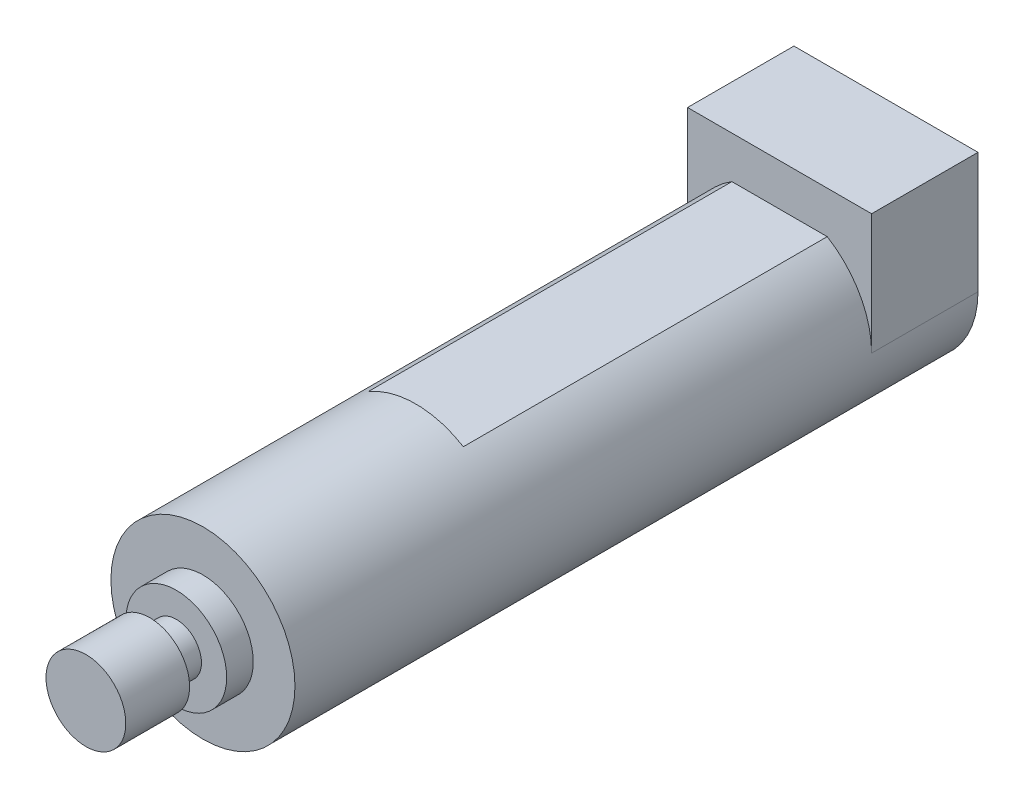
SolidWorks part; units mm, degrees
ref_plane "Front Plane" through (0, 0, 0) normal (0, 0, 1) x (1, 0, 0)
ref_plane "Top Plane" through (0, 0, 0) normal (0, 1, 0) x (1, 0, 0)
ref_plane "Right Plane" through (0, 0, 0) normal (1, 0, 0) x (0, 0, -1)
sketch "Sketch1" plane through (0, 0, 0) normal (0, 0, 1) x (1, 0, 0)
  line L0 (-10.9855, 0) -> (-10.9855, 14.4145)
  line L1 (-10.9855, 14.4145) -> (10.9855, 14.4145)
  line L2 (10.9855, 14.4145) -> (10.9855, 0)
  arc A0 (-10.9855, 0) -> (10.9855, 0) centre (0, 0) ccw
  dimension "D1" = 21.971
  dimension "D2" = 14.4145
extrude "Boss-Extrude1" add sketch "Sketch1" along normal blind 12.7
sketch "Sketch2" plane through (0, 0, 12.7) normal (0, 0, 1) x (1, 0, 0)
  line L0 (-5.6885, 9.398) -> (5.6885, 9.398)
  line L1 (0, 0) -> (22.0029, 0) construction
  line L2 (-5.6885, -9.398) -> (5.6885, -9.398)
  arc A0 (-5.6885, 9.398) -> (-5.6885, -9.398) centre (0, 0) ccw
  arc A1 (5.6885, -9.398) -> (5.6885, 9.398) centre (0, 0) ccw
  arc A2 (-10.9855, 0) -> (10.9855, 0) centre (0, 0) ccw construction
  dimension "D1" = 9.398
extrude "Boss-Extrude2" add sketch "Sketch2" along normal blind 43.434
sketch "Sketch3" plane through (0, 0, 56.134) normal (0, 0, 1) x (1, 0, 0)
  circle A0 centre (0, 0) radius 10.9855
extrude "Boss-Extrude3" add sketch "Sketch3" along normal blind 25.4
sketch "Sketch4" plane through (0, 0, 81.534) normal (0, 0, 1) x (1, 0, 0)
  circle A0 centre (0, 0) radius 6.0071
  dimension "D1" = 12.0142
extrude "Boss-Extrude4" add sketch "Sketch4" along normal blind 3.175
sketch "Sketch5" plane through (0, 0, 84.709) normal (0, 0, 1) x (1, 0, 0)
  circle A0 centre (0, 0) radius 2.9972
  dimension "D1" = 5.9944
extrude "Boss-Extrude5" add sketch "Sketch5" along normal blind 3.175
sketch "Sketch6" plane through (0, 0, 87.884) normal (0, 0, 1) x (1, 0, 0)
  circle A0 centre (0, 0) radius 4.7625
  dimension "D1" = 9.525
extrude "Boss-Extrude6" add sketch "Sketch6" along normal blind 7.62
